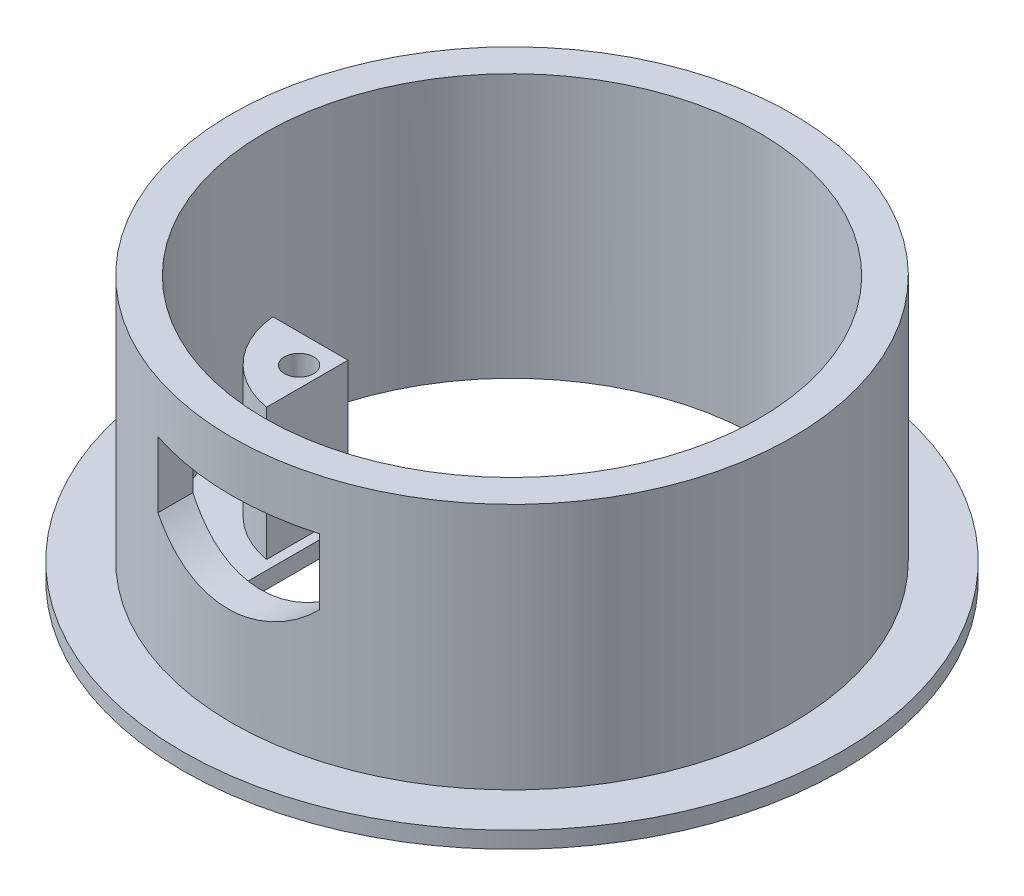
SolidWorks part; units mm, degrees
ref_plane "Front Plane" through (0, 0, 0) normal (0, 0, 1) x (1, 0, 0)
ref_plane "Top Plane" through (0, 0, 0) normal (0, 1, 0) x (1, 0, 0)
ref_plane "Right Plane" through (0, 0, 0) normal (1, 0, 0) x (0, 0, -1)
sketch "Sketch1" plane through (0, 0, 0) normal (0, 1, 0) x (1, 0, 0)
  circle A0 centre (0, 0) radius 40
  circle A1 centre (0, 0) radius 30
  dimension "D1" = 80
  dimension "D2" = 60
extrude "Boss-Extrude1" add sketch "Sketch1" along normal blind 2
sketch "Sketch2" plane through (0, 2, 0) normal (0, 1, 0) x (1, 0, 0)
  circle A0 centre (0, 0) radius 30 construction
  circle A1 centre (0, 0) radius 30
  circle A2 centre (0, 0) radius 34
  dimension "D1" = 4
extrude "Boss-Extrude2" add sketch "Sketch2" along normal blind 30
ref_plane "Plane1" through (0, 12, 0) normal (0, 1, 0) x (1, 0, 0)
sketch "Sketch9" plane through (0, 0, 0) normal (0, 1, 0) x (1, 0, 0)
  line L0 (-29.8657, -2.8351) -> (29.8657, -2.8351)
  line L1 (0, 30) -> (0, -48.3805) construction
  line L2 (-30, 0) -> (59.405, 0) construction
  circle A0 centre (0, 0) radius 30 construction
  arc A1 (29.8657, -2.8351) -> (0, -30) centre (0, 0) cw
  arc A2 (-29.8657, -2.8351) -> (0, -30) centre (0, 0) ccw
extrude "Boss-Extrude3" add sketch "Sketch9" along normal blind 2
sketch "Sketch11" plane through (0, 2, 0) normal (0, 1, 0) x (1, 0, 0)
  line L0 (-24.1735, -4.8351) -> (-15.0625, -4.8351)
  line L1 (-15.0625, -4.8351) -> (-15.0625, -14.7177)
  line L2 (0, 30) -> (0, 39.1404) construction
  line L3 (24.1735, -4.8351) -> (15.0625, -4.8351)
  line L4 (15.0625, -4.8351) -> (15.0625, -14.7177)
  line L5 (-29.8657, -2.8351) -> (29.8657, -2.8351) construction
  arc A0 (-24.1735, -4.8351) -> (-15.0625, -14.7177) centre (-13.1735, -3.8351) ccw
  arc A1 (24.1735, -4.8351) -> (15.0625, -14.7177) centre (13.1735, -3.8351) cw
  dimension "D1" = 2
ref_plane "Plane2" through (0, 0, 35) normal (0, 0, 1) x (1, 0, 0)
sketch "Sketch10" plane through (0, 0, 35) normal (0, 0, 1) x (1, 0, 0)
  line L0 (-10.6683, 25.8895) -> (9.3317, 25.8895)
  line L1 (9.3317, 25.8895) -> (9.3317, 17.8895)
  line L2 (-10.6683, 25.8895) -> (-10.6683, 17.8895)
  arc A0 (9.3317, 17.8895) -> (-10.6683, 17.8895) centre (-0.6683, 27.8895) cw
extrude "Cut-Extrude1" cut sketch "Sketch10" against normal blind 7
extrude "Boss-Extrude4" add sketch "Sketch11" along normal blind 16
sketch "Sketch12" plane through (0, 18, 0) normal (0, 1, 0) x (1, 0, 0)
  line L0 (0, 0) -> (0, 7.1822) construction
  line L1 (0, 30) -> (0, -48.3805) construction
  line L2 (-15.0625, -4.8351) -> (-24.1735, -4.8351) construction
  circle A0 centre (-17.5, -8.3351) radius 1.775
  circle A1 centre (17.5, -8.3351) radius 1.775
  dimension "D1" = 35
  dimension "D2" = 3.5
extrude "Cut-Extrude2" cut sketch "Sketch12" against normal blind 9
sketch "Sketch13" plane through (0, 2, 0) normal (0, 1, 0) x (1, 0, 0)
  line L0 (-13.9184, -20.8807) -> (-13.9184, 1.1193)
  line L1 (-13.9184, 1.1193) -> (14.0816, 1.1193)
  line L2 (14.0816, 1.1193) -> (14.0816, -20.8807)
  arc A0 (14.0816, -20.8807) -> (-13.9184, -20.8807) centre (0.0816, -8.9643) cw
  dimension "D1" = 28
extrude "Cut-Extrude3" cut sketch "Sketch13" against normal blind 10
